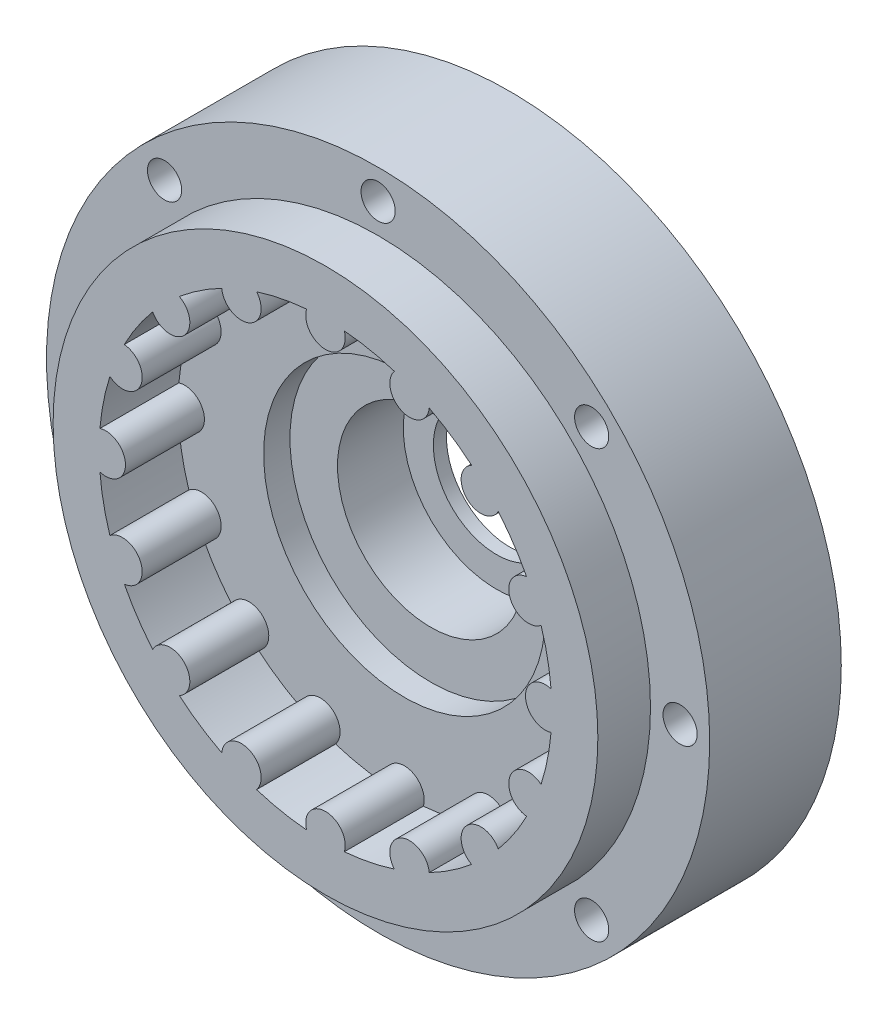
SolidWorks part; units mm, degrees
material "ABS"
ref_plane "Front Plane" through (0, 0, 0) normal (0, 0, 1) x (1, 0, 0)
ref_plane "Top Plane" through (0, 0, 0) normal (0, 1, 0) x (1, 0, 0)
ref_plane "Right Plane" through (0, 0, 0) normal (1, 0, 0) x (0, 0, -1)
sketch "Sketch1" plane through (0, 0, 0) normal (0, 0, 1) x (1, 0, 0)
  circle A0 centre (0, 0) radius 32.004
  dimension "D1" = 64.008
extrude "Boss-Extrude1" add sketch "Sketch1" along normal blind 12.7
sketch "Sketch2" plane through (0, 0, 12.7) normal (0, 0, 1) x (1, 0, 0)
  circle A0 centre (0, 0) radius 26.289
  circle A1 centre (0, 0) radius 32.004
  circle A2 centre (0, 0) radius 32.004
  dimension "D1" = 0
  dimension "D2" = 5.715
extrude "Cut-Extrude1" cut sketch "Sketch2" against normal blind 2.54 flip side to cut
sketch "Sketch3" plane through (0, 0, 10.16) normal (0, 0, 1) x (1, 0, 0)
  line L0 (0, 0) -> (0, 21.209) construction
  circle A1 centre (0, 21.209) radius 1.905
  circle A3 centre (0, 0) radius 21.209 construction
  circle A13 centre (8.1163, 19.5946) radius 1.905
  circle A14 centre (14.997, 14.997) radius 1.905
  circle A15 centre (19.5946, 8.1163) radius 1.905
  circle A16 centre (21.209, 0) radius 1.905
  circle A17 centre (19.5946, -8.1163) radius 1.905
  circle A18 centre (14.997, -14.997) radius 1.905
  circle A19 centre (8.1163, -19.5946) radius 1.905
  circle A20 centre (0, -21.209) radius 1.905
  circle A21 centre (-8.1163, -19.5946) radius 1.905
  circle A22 centre (-14.997, -14.997) radius 1.905
  circle A23 centre (-19.5946, -8.1163) radius 1.905
  circle A24 centre (-21.209, 0) radius 1.905
  circle A25 centre (-19.5946, 8.1163) radius 1.905
  circle A26 centre (-14.997, 14.997) radius 1.905
  circle A27 centre (-8.1163, 19.5946) radius 1.905
  dimension "D2" = 3.81
  dimension "D3" = 16
  dimension "D1" = 42.418
  dimension "D4" = 21.209
sketch "Sketch4" plane through (0, 0, 10.16) normal (0, 0, 1) x (1, 0, 0)
  circle A39 centre (0, 0) radius 27.559 construction
  circle A40 centre (0, 0) radius 13.589
  circle A41 centre (0, 0) radius 26.289 construction
  dimension "D2" = 55.118
  dimension "D1" = 13.97
extrude "Cut-Extrude3" cut sketch "Sketch4" against normal blind 2.54 contours A40 region at (0, 0, 10.16)
sketch "Sketch5" plane through (0, 0, 7.62) normal (0, 0, 1) x (1, 0, 0)
  circle A0 centre (0, 0) radius 9
  circle A1 centre (0, 0) radius 6.1
  dimension "D1" = 18
  dimension "D2" = 12.2
extrude "Cut-Extrude4" cut sketch "Sketch5" against normal through all contours A1 region at (0, 0, 7.62)
sketch "Sketch6" plane through (0, 0, 12.7) normal (0, 0, 1) x (1, 0, 0)
  line L0 (0, 0) -> (0, 32.004) construction
  line L1 (0, 0) -> (22.6302, 22.6302) construction
  line L2 (0, 0) -> (32.004, 0) construction
  line L3 (0, 0) -> (22.6302, -22.6302) construction
  line L4 (0, 0) -> (0, -32.004) construction
  line L5 (0, 0) -> (-22.6302, -22.6302) construction
  line L6 (0, 0) -> (-32.004, 0) construction
  line L7 (0, 0) -> (-22.6302, 22.6302) construction
  line L8 (0, 0) -> (0, 29.1465) construction
  circle A0 centre (0, 0) radius 32.004 construction
  point P6 (0, 29.1465)
  point P16 (20.6097, 20.6097)
  point P18 (29.1465, 0)
  point P20 (20.6097, -20.6097)
  point P22 (0, -29.1465)
  point P24 (-20.6097, -20.6097)
  point P26 (-29.1465, 0)
  point P28 (-20.6097, 20.6097)
  dimension "D1" = 29.1465
  dimension "D2" = 8
hole_wizard "M4x0.7 Tapped Hole1" positions "Sketch6" profile "Sketch7" tap size "M4x0.7" standard "ANSI Metric" end condition through all
sketch "Sketch7" plane through (-20.6097, 20.6097, 12.7) normal (1, 0, 0) x (0, -1, 0)
  line L0 (0, 0) -> (0, 12.7)
  line L1 (0, 12.7) -> (1.65, 12.7)
  line L2 (1.65, 12.7) -> (1.65, 0)
  line L5 (1.65, 0) -> (0, 0)
  line L11 (0, -6.35) -> (0, 107.95) construction
  dimension "Thru Tap Drill Dia." = 3.3
  dimension "Thru Tap Drill Depth" = 12.7
cosmetic thread "Hole Thread1" parameters "D2"=4
cosmetic thread "Hole Thread2" parameters "D2"=4
cosmetic thread "Hole Thread3" parameters "D2"=4
cosmetic thread "Hole Thread4" parameters "D2"=4
cosmetic thread "Hole Thread5" parameters "D2"=4
cosmetic thread "Hole Thread6" parameters "D2"=4
cosmetic thread "Hole Thread7" parameters "D2"=4
cosmetic thread "Hole Thread8" parameters "D2"=4
extrude "Cut-Extrude5" cut sketch "Sketch5<3>" against normal blind 6.35
sketch "Sketch5<3>" plane through (0, 0, 7.62) normal (0, 0, 1) x (1, 0, 0) same geometry as "Sketch5"
sketch "Sketch8" plane through (0, 0, 10.16) normal (0, 0, 1) x (1, 0, 0)
  circle A0 centre (0, 0) radius 21.844
  circle A1 centre (0, 0) radius 26.289
  circle A5 centre (0, 0) radius 26.289
  dimension "D1" = 0
extrude "Boss-Extrude2" add sketch "Sketch8" along normal blind 7.62
extrude "Boss-Extrude3" add sketch "Sketch3" along normal blind 7.62
